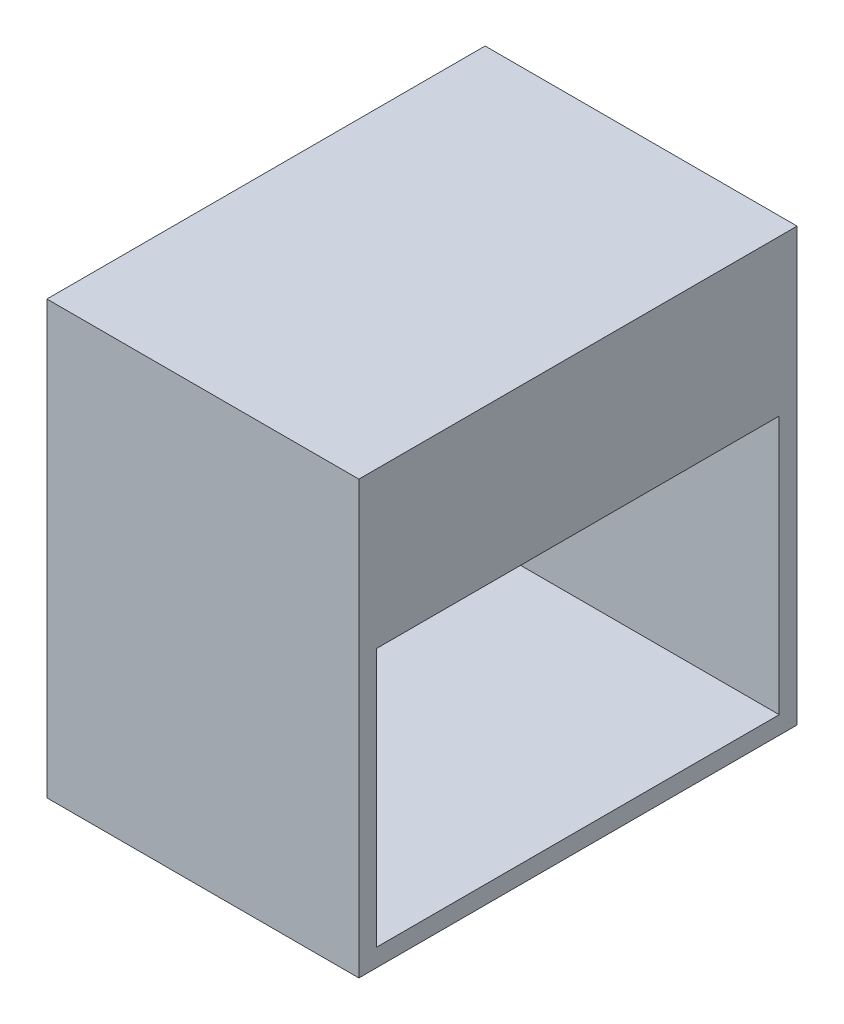
SolidWorks part; units mm, degrees
ref_plane "Front Plane" through (0, 0, 0) normal (0, 0, 1) x (1, 0, 0)
ref_plane "Top Plane" through (0, 0, 0) normal (0, 1, 0) x (1, 0, 0)
ref_plane "Right Plane" through (0, 0, 0) normal (1, 0, 0) x (0, 0, -1)
sketch "Sketch1" plane through (0, 0, 0) normal (0, 1, 0) x (1, 0, 0)
  line L0 (0, 0) -> (370.946, 0)
  line L1 (0, 0) -> (0, 521.0796)
  line L2 (370.946, 0) -> (370.946, 521.0796)
  line L3 (0, 521.0796) -> (370.946, 521.0796)
  dimension "D1" = 521.0796
  dimension "D2" = 370.946
extrude "Boss-Extrude1" add sketch "Sketch1" along normal blind 0.6096
sketch "Sketch3" plane through (0, 0.6096, 0) normal (0, 1, 0) x (1, 0, 0)
  line L0 (0, 521.0796) -> (0, 0) construction
  line L1 (0, 521.0796) -> (0, 0)
  line L2 (0.6096, 521.0796) -> (0.6096, 0)
  line L3 (0, 0) -> (370.946, 0) construction
  line L4 (0, 0) -> (0.6096, 0)
  line L5 (370.946, 521.0796) -> (0, 521.0796) construction
  line L6 (0.6096, 521.0796) -> (0, 521.0796)
  dimension "D1" = 0.6096
extrude "Boss-Extrude2" add sketch "Sketch3" along normal blind 512.5296
sketch "Sketch4" plane through (0, 0.6096, 0) normal (0, 1, 0) x (1, 0, 0)
  line L0 (0.6096, 0) -> (370.946, 0) construction
  line L1 (0.6096, 0) -> (370.946, 0)
  line L2 (0.6096, 0.6096) -> (370.946, 0.6096)
  line L3 (370.946, 0) -> (370.946, 521.0796) construction
  line L4 (370.946, 0) -> (370.946, 0.6096)
  line L5 (0.6096, 0) -> (0.6096, 521.0796) construction
  line L6 (0.6096, 0) -> (0.6096, 0.6096)
  dimension "D1" = 0.6096
extrude "Boss-Extrude3" add sketch "Sketch4" along normal blind 512.5296
sketch "Sketch6" plane through (0, 0.6096, 0) normal (0, 1, 0) x (1, 0, 0)
  line L1 (370.946, 0.6096) -> (370.3364, 0.6096)
  line L2 (370.946, 0.6096) -> (370.946, 520.47)
  line L3 (370.946, 520.47) -> (370.3364, 520.47)
  line L4 (370.3364, 0.6096) -> (370.3364, 520.47)
  dimension "D1" = 0.6096
  dimension "D2" = 519.8604
extrude "Boss-Extrude4" add sketch "Sketch6" along normal blind 20
sketch "Sketch8" plane through (0, 0.6096, 0) normal (0, 1, 0) x (1, 0, 0)
  line L1 (0.6096, 521.0796) -> (370.946, 521.0796)
  line L2 (0.6096, 521.0796) -> (0.6096, 520.47)
  line L3 (0.6096, 520.47) -> (370.946, 520.47)
  line L4 (370.946, 521.0796) -> (370.946, 520.47)
  line L5 (370.946, 520.47) -> (370.946, 521.0796) construction
  dimension "D1" = 0.6096
extrude "Boss-Extrude5" add sketch "Sketch8" along normal up to surface (512.5296 mm away) up to face at (123.8519, 513.1392, -173.8964)
sketch "Sketch9" plane through (0, 513.1392, 0) normal (0, 1, 0) x (1, 0, 0)
  line L1 (0, 0) -> (370.946, 0)
  line L2 (0, 0) -> (0, 521.0796)
  line L3 (0, 521.0796) -> (370.946, 521.0796)
  line L4 (370.946, 0) -> (370.946, 521.0796)
extrude "Boss-Extrude6" add sketch "Sketch9" along normal blind 0.6096
sketch "Sketch11" plane through (0, 513.1392, 0) normal (0, -1, 0) x (1, 0, 0)
  line L0 (0.6096, -520.47) -> (370.946, -520.47) construction
  line L1 (370.946, -0.6096) -> (370.3364, -0.6096)
  line L2 (370.946, -0.6096) -> (370.946, -520.47)
  line L3 (370.946, -520.47) -> (370.3364, -520.47)
  line L4 (370.3364, -0.6096) -> (370.3364, -520.47)
  dimension "D1" = 0.6096
extrude "Boss-Extrude7" add sketch "Sketch11" along normal blind 183.7036
sketch "Sketch10" plane through (0, 20.6096, 0) normal (0, 1, 0) x (1, 0, 0)
  line L0 (370.946, 0.6096) -> (370.946, 520.47) construction
  line L1 (370.3364, 0.6096) -> (370.946, 0.6096)
  line L2 (370.3364, 0.6096) -> (370.3364, 20.6096)
  line L3 (370.3364, 20.6096) -> (370.946, 20.6096)
  line L4 (370.946, 0.6096) -> (370.946, 20.6096)
  line L5 (370.3364, 520.47) -> (370.3364, 0.6096) construction
  line L6 (370.946, 520.47) -> (370.3364, 520.47)
  line L7 (370.946, 520.47) -> (370.946, 500.47)
  line L8 (370.946, 500.47) -> (370.3364, 500.47)
  line L9 (370.3364, 520.47) -> (370.3364, 500.47)
  dimension "D1" = 20
  dimension "D2" = 20
extrude "Boss-Extrude8" add sketch "Sketch10" along normal up to surface (308.826 mm away) up to face at (370.6412, 329.4356, -260.5398)
sketch "Sketch13" plane through (370.946, 0, 0) normal (1, 0, 0) x (0, 0, -1)
  line L0 (500.47, 329.4356) -> (500.47, 20.6096) construction
  line L1 (20.6096, 20.6096) -> (500.47, 20.6096)
  line L2 (20.6096, 20.6096) -> (20.6096, 21.2192)
  line L3 (20.6096, 21.2192) -> (500.47, 21.2192)
  line L4 (500.47, 20.6096) -> (500.47, 21.2192)
  dimension "D1" = 0.6096
extrude "Boss-Extrude9" add sketch "Sketch13" against normal blind 350.34
sketch "Sketch14" plane through (0, 21.2192, 0) normal (0, 1, 0) x (1, 0, 0)
  line L0 (20.606, 500.47) -> (370.3364, 500.47) construction
  line L1 (20.606, 20.6096) -> (21.2156, 20.6096)
  line L2 (20.606, 20.6096) -> (20.606, 500.47)
  line L3 (20.606, 500.47) -> (21.2156, 500.47)
  line L4 (21.2156, 20.6096) -> (21.2156, 500.47)
  dimension "D1" = 0.6096
extrude "Boss-Extrude10" add sketch "Sketch14" along normal up to surface (491.92 mm away) up to face at (185.473, 513.1392, -260.5398)
sketch "Sketch15" plane through (0, 21.2192, 0) normal (0, 1, 0) x (1, 0, 0)
  line L0 (370.946, 500.47) -> (370.946, 20.6096) construction
  line L1 (21.2156, 20.6096) -> (370.946, 20.6096)
  line L2 (21.2156, 20.6096) -> (21.2156, 21.2192)
  line L3 (21.2156, 21.2192) -> (370.946, 21.2192)
  line L4 (370.946, 20.6096) -> (370.946, 21.2192)
  line L6 (21.2156, 500.47) -> (370.946, 500.47)
  line L7 (21.2156, 500.47) -> (21.2156, 499.8604)
  line L8 (21.2156, 499.8604) -> (370.946, 499.8604)
  line L9 (370.946, 500.47) -> (370.946, 499.8604)
  dimension "D1" = 0.6096
  dimension "D2" = 0.6096
extrude "Boss-Extrude11" add sketch "Sketch15" along normal up to surface (491.92 mm away) up to face at (185.473, 513.1392, -260.5398)
sketch "Sketch17" plane through (370.946, 0, 0) normal (1, 0, 0) x (0, 0, -1)
  line L0 (499.8604, 329.4356) -> (499.8604, 21.2192) construction
  line L1 (21.2192, 329.4356) -> (499.8604, 329.4356)
  line L2 (21.2192, 329.4356) -> (21.2192, 328.826)
  line L3 (21.2192, 328.826) -> (499.8604, 328.826)
  line L4 (499.8604, 329.4356) -> (499.8604, 328.826)
  dimension "D1" = 0.6096
extrude "Boss-Extrude12" add sketch "Sketch17" against normal blind 20
